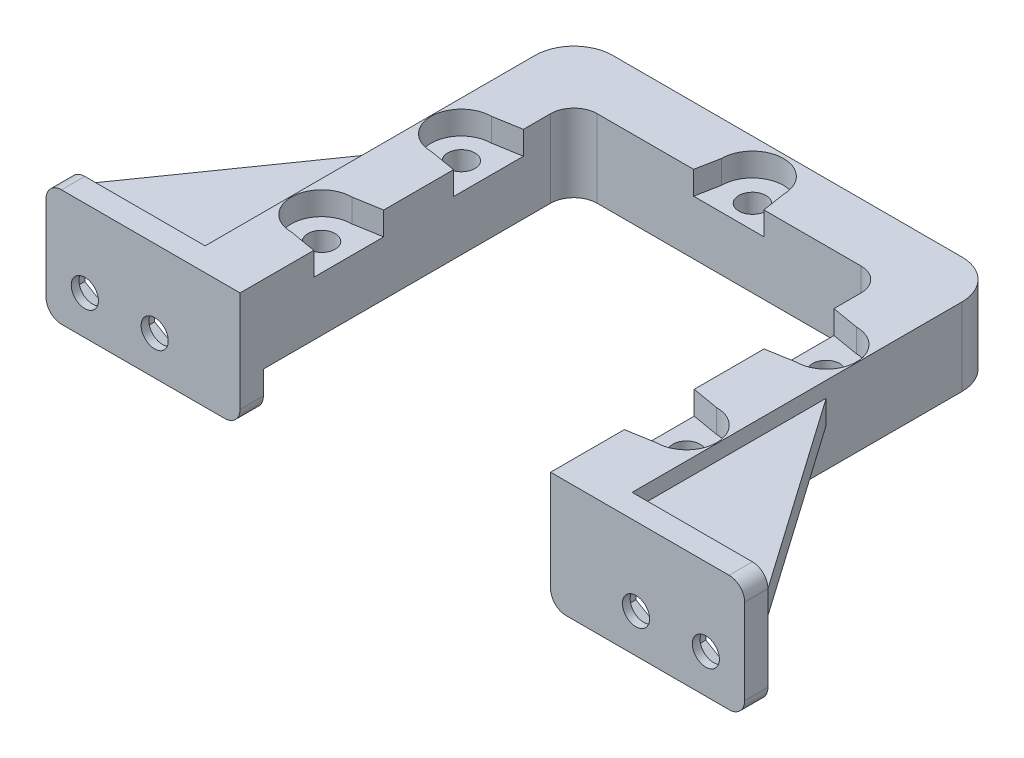
SolidWorks part; units mm, degrees
ref_plane "Front Plane" through (0, 0, 0) normal (0, 0, 1) x (1, 0, 0)
ref_plane "Top Plane" through (0, 0, 0) normal (0, 1, 0) x (1, 0, 0)
ref_plane "Right Plane" through (0, 0, 0) normal (1, 0, 0) x (0, 0, -1)
sketch "Sketch1" plane through (0, 0, 0) normal (0, 1, 0) x (1, 0, 0)
  line L0 (-20, -20) -> (-27.5, -20)
  line L1 (-17, 20) -> (17, 20)
  line L2 (-20, 17) -> (-20, -20)
  line L4 (20, 17) -> (20, -20)
  line L5 (-20, 20) -> (20, -20) construction
  line L6 (-20, -20) -> (20, 20) construction
  line L7 (-22.5, 27.5) -> (22.5, 27.5)
  line L8 (-27.5, 22.5) -> (-27.5, -20)
  line L10 (27.5, 22.5) -> (27.5, -20)
  line L11 (-27.5, 27.5) -> (27.5, -27.5) construction
  line L12 (-27.5, -27.5) -> (27.5, 27.5) construction
  line L13 (20, -20) -> (27.5, -20)
  line L14 (-20, -20) -> (20, -20) construction
  arc A0 (17, 20) -> (20, 17) centre (17, 17) cw
  arc A1 (-17, 20) -> (-20, 17) centre (-17, 17) ccw
  arc A2 (22.5, 27.5) -> (27.5, 22.5) centre (22.5, 22.5) cw
  arc A3 (-22.5, 27.5) -> (-27.5, 22.5) centre (-22.5, 22.5) ccw
  point P0 (0, 0)
  point P12 (0, 0)
  point P18 (0, 0)
  dimension "D3" = 3
  dimension "D6" = 5
  dimension "D1" = 40
  dimension "D2" = 40
  dimension "D4" = 55
  dimension "D5" = 55
  dimension "D9" = 7.5
extrude "Boss-Extrude1" add sketch "Sketch1" along normal blind 10
sketch "Sketch2" plane through (0, 10, 0) normal (0, 1, 0) x (1, 0, 0)
  line L0 (-23.5, -9) -> (23.5, -9) construction
  line L1 (0, -9) -> (0, -20) construction
  line L4 (-20, -20) -> (20, -20) construction
  line L5 (0, 20) -> (0, 23) construction
  line L6 (-17, 20) -> (17, 20) construction
  line L7 (-23.5, 9) -> (23.5, 9) construction
  line L8 (0, 9) -> (0, 20) construction
  circle A0 centre (-23.5, -9) radius 1.75
  circle A1 centre (23.5, -9) radius 1.75
  circle A2 centre (0, 23) radius 1.75
  circle A3 centre (-23.5, 9) radius 1.75
  circle A4 centre (23.5, 9) radius 1.75
  dimension "D3" = 3.5
  dimension "D4" = 3.5
  dimension "D6" = 3.5
  dimension "D9" = 3.5
  dimension "D10" = 3.5
  dimension "D1" = 11
  dimension "D2" = 47
  dimension "D5" = 3
  dimension "47" = 47
  dimension "D8" = 11
extrude "Cut-Extrude1" cut sketch "Sketch2" against normal blind 15.5
sketch "Sketch3" plane through (0, 0, 0) normal (0, -1, 0) x (1, 0, 0)
  line L1 (-20.6, 7.3257) -> (-20.6, 10.6743)
  line L2 (-20.6, 10.6743) -> (-23.5, 12.3486)
  line L3 (-23.5, 12.3486) -> (-26.4, 10.6743)
  line L4 (-26.4, 10.6743) -> (-26.4, 7.3257)
  line L5 (-26.4, 7.3257) -> (-23.5, 5.6514)
  line L6 (-23.5, 5.6514) -> (-20.6, 7.3257)
  line L7 (23.4997, 5.6514) -> (26.3998, 7.3254)
  line L8 (26.3998, 7.3254) -> (26.4002, 10.674)
  line L9 (26.4002, 10.674) -> (23.5003, 12.3486)
  line L10 (23.5003, 12.3486) -> (20.6002, 10.6746)
  line L11 (20.6002, 10.6746) -> (20.5998, 7.326)
  line L12 (20.5998, 7.326) -> (23.4997, 5.6514)
  line L13 (3.3486, -23) -> (1.6743, -20.1)
  line L14 (1.6743, -20.1) -> (-1.6743, -20.1)
  line L15 (-1.6743, -20.1) -> (-3.3486, -23)
  line L16 (-3.3486, -23) -> (-1.6743, -25.9)
  line L17 (-1.6743, -25.9) -> (1.6743, -25.9)
  line L18 (1.6743, -25.9) -> (3.3486, -23)
  line L19 (-23.4997, -5.6514) -> (-26.3998, -7.3254)
  line L20 (-26.3998, -7.3254) -> (-26.4002, -10.674)
  line L21 (-26.4002, -10.674) -> (-23.5003, -12.3486)
  line L22 (-23.5003, -12.3486) -> (-20.6002, -10.6746)
  line L23 (-20.6002, -10.6746) -> (-20.5998, -7.326)
  line L24 (-20.5998, -7.326) -> (-23.4997, -5.6514)
  line L25 (23.4997, -5.6514) -> (20.5998, -7.326)
  line L26 (20.5998, -7.326) -> (20.6002, -10.6746)
  line L27 (20.6002, -10.6746) -> (23.5003, -12.3486)
  line L28 (23.5003, -12.3486) -> (26.4002, -10.674)
  line L29 (26.4002, -10.674) -> (26.3998, -7.3254)
  line L30 (26.3998, -7.3254) -> (23.4997, -5.6514)
  circle A0 centre (-23.5, 9) radius 2.9 construction
  circle A1 centre (23.5, 9) radius 2.9 construction
  circle A2 centre (0, -23) radius 2.9 construction
  circle A3 centre (-23.5, -9) radius 2.9 construction
  circle A4 centre (23.5, -9) radius 2.9 construction
  dimension "D1" = 5.8
  dimension "D2" = 5.8
  dimension "D3" = 5.8
  dimension "D4" = 5.8
  dimension "D5" = 5.8
extrude "Cut-Extrude2" cut sketch "Sketch3" against normal blind 3
sketch "Sketch8" plane through (0, 10, 0) normal (0, 1, 0) x (1, 0, 0)
  line L0 (-4, 23) -> (-4.5746, 20)
  line L1 (-17, 20) -> (17, 20) construction
  line L2 (-4.5746, 20) -> (4.4783, 20)
  line L3 (4.4783, 20) -> (4, 23)
  line L4 (23.5, 12.9) -> (20, 13.5)
  line L5 (20, 17) -> (20, -20) construction
  line L6 (20, 13.5) -> (20, 4.5)
  line L7 (20, 4.5) -> (23.5, 5.1)
  line L8 (23.5, -5.1) -> (20, -4.5)
  line L9 (20, -4.5) -> (20, -13.5)
  line L10 (20, -13.5) -> (23.5, -12.9)
  line L11 (-23.5, -12.9) -> (-20, -13.5)
  line L12 (-20, -20) -> (-20, 17) construction
  line L13 (-20, -13.5) -> (-20, -4.5)
  line L14 (-20, -4.5) -> (-23.5, -5.1)
  line L15 (-20, -9) -> (-23.5, -9) construction
  line L16 (20, -9) -> (23.5, -9) construction
  line L17 (20, 9) -> (23.5, 9) construction
  line L18 (-0.0481, 20) -> (0, 23) construction
  line L19 (-23.5, 12.9) -> (-20, 13.5)
  line L20 (-20, 13.5) -> (-20, 4.5)
  line L21 (-20, 4.5) -> (-23.5, 5.1)
  line L22 (-23.5, 9) -> (-20, 9) construction
  arc A0 (4, 23) -> (-4, 23) centre (0, 23) ccw
  arc A1 (-23.5, 12.9) -> (-23.5, 5.1) centre (-23.5, 9) ccw
  arc A2 (-23.5, -5.1) -> (-23.5, -12.9) centre (-23.5, -9) ccw
  arc A4 (23.5, -12.9) -> (23.5, -5.1) centre (23.5, -9) ccw
  arc A5 (23.5, 5.1) -> (23.5, 12.9) centre (23.5, 9) ccw
  dimension "D1" = 9
  dimension "D2" = 9
  dimension "D3" = 9
  dimension "D4" = 9
extrude "Cut-Extrude7" cut sketch "Sketch8" against normal blind 3
sketch "Sketch9" plane through (0, 0, 20) normal (0, 0, 1) x (1, 0, 0)
  line L0 (-20, 10) -> (-20, -5)
  line L1 (-20, 10) -> (-45, 10)
  line L2 (-20, -5) -> (-45, -5)
  line L3 (-45, 10) -> (-45, -5)
  dimension "D1" = 25
  dimension "D2" = 15
extrude "Boss-Extrude2" add sketch "Sketch9" along normal blind 3
sketch "Sketch11" plane through (0, 0, 20) normal (0, 0, -1) x (-1, 0, 0)
  line L0 (45, 10) -> (45, -5) construction
  line L1 (45, 8) -> (27.5, 8)
  line L2 (45, 8) -> (45, 5)
  line L3 (45, 5) -> (27.5, 5)
  line L4 (27.5, 8) -> (27.5, 5)
  line L5 (27.5, 10) -> (27.5, 0) construction
  line L6 (45, -5) -> (20, -5) construction
  dimension "D1" = 3
  dimension "D2" = 10
extrude "Boss-Extrude4" add sketch "Sketch11" along normal blind 25
sketch "Sketch13" plane through (0, 5, 0) normal (0, -1, 0) x (1, 0, 0)
  line L0 (-45, 20) -> (-27.5, -5)
  line L1 (-27.5, -5) -> (-45, -5)
  line L2 (-45, -5) -> (-45, 20)
extrude "Cut-Extrude9" cut sketch "Sketch13" against normal blind 25
fillet "Fillet2" radius 2 3 edges at (-20, -5, 21.5) (-45, 10, 21.5) (-45, -5, 21.5)
sketch "Sketch14" plane through (0, 0, 20) normal (0, 0, -1) x (-1, 0, 0)
  line L0 (31, 0) -> (40, 0) construction
  line L1 (40, 0) -> (45, 0) construction
  line L2 (45, 5) -> (45, -3) construction
  circle A0 centre (40, 0) radius 1.75
  circle A1 centre (31, 0) radius 1.75
  dimension "D1" = 3.5
  dimension "D2" = 3.5
  dimension "D3" = 5
  dimension "D4" = 9
extrude "Cut-Extrude10" cut sketch "Sketch14" against normal through all
sketch "Sketch15" plane through (0, 0, 20) normal (0, 0, -1) x (-1, 0, 0)
  line L1 (31, 3.4641) -> (28, 1.7321)
  line L2 (28, 1.7321) -> (28, -1.7321)
  line L3 (28, -1.7321) -> (31, -3.4641)
  line L4 (31, -3.4641) -> (34, -1.7321)
  line L5 (34, -1.7321) -> (34, 1.7321)
  line L6 (34, 1.7321) -> (31, 3.4641)
  line L7 (40, 3.4641) -> (37, 1.7321)
  line L8 (37, 1.7321) -> (37, -1.7321)
  line L9 (37, -1.7321) -> (40, -3.4641)
  line L10 (40, -3.4641) -> (43, -1.7321)
  line L11 (43, -1.7321) -> (43, 1.7321)
  line L12 (43, 1.7321) -> (40, 3.4641)
  circle A0 centre (31, 0) radius 3 construction
  circle A1 centre (40, 0) radius 3 construction
  dimension "D1" = 6
  dimension "D2" = 6
extrude "Cut-Extrude11" cut sketch "Sketch15" against normal blind 2
mirror "Mirror1" about plane through (0, 0, 0) normal (1, 0, 0) of "Cut-Extrude11", "Cut-Extrude10", "Fillet2", "Cut-Extrude9", "Boss-Extrude4", "Boss-Extrude2"
